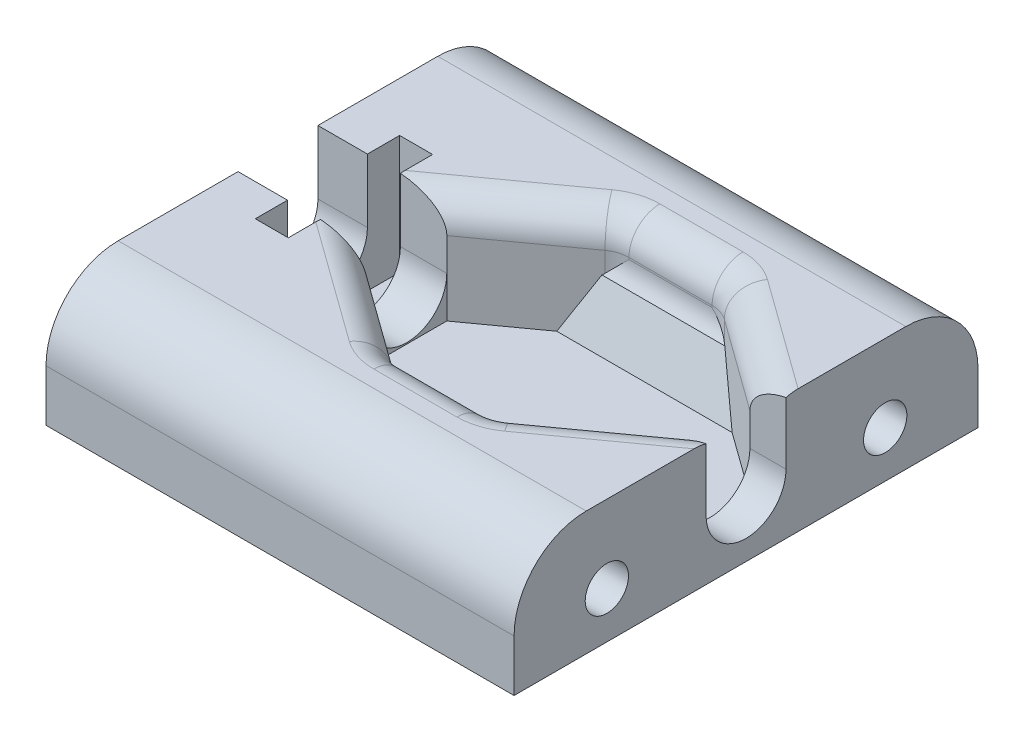
SolidWorks part; units mm, degrees
other "Markup1"
sketch "Sketch10" plane through (217, 42, -42) normal (0.057, 0.9883, -0.1416) x (-0.9984, 0.0574, -0.0017)
sketch "Sketch71" plane through (218, 42, -54.5) normal (0.057, 0.9883, -0.1416) x (-0.9984, 0.0574, -0.0017)
sketch "Sketch77" plane through (218, 42, -45) normal (0.057, 0.9883, -0.1416) x (-0.9984, 0.0574, -0.0017)
ref_plane "Front Plane" through (0, 0, 0) normal (0, 0, 1) x (1, 0, 0)
ref_plane "Top Plane" through (0, 0, 0) normal (0, 1, 0) x (1, 0, 0)
ref_plane "Right Plane" through (0, 0, 0) normal (1, 0, 0) x (0, 0, -1)
sketch "Sketch1" plane through (0, 0, 0) normal (0, 1, 0) x (1, 0, 0)
  line L1 (0, 0) -> (218, 0)
  line L2 (0, 0) -> (0, 45)
  line L3 (0, 45) -> (218, 45)
  line L4 (218, 0) -> (218, 45)
  dimension "D1" = 45
  dimension "D2" = 218
extrude "Boss-Extrude1" add sketch "Sketch1" along normal blind 42
sketch "Sketch7" plane through (0, 42, 0) normal (0, 1, 0) x (1, 0, 0)
  line L0 (218, 45) -> (0, 45) construction
  line L1 (9, 43.5) -> (127.2, 43.5)
  line L2 (9, 43.5) -> (9, 1.5)
  line L3 (9, 1.5) -> (127.2, 1.5)
  line L4 (127.2, 43.5) -> (127.2, 1.5)
  line L5 (0, 0) -> (218, 0) construction
  line L7 (0, 45) -> (0, 0) construction
  dimension "D1" = 1.5
  dimension "D2" = 1.5
  dimension "D3" = 9
  dimension "D4" = 118.2
extrude "Cut-Extrude17" cut sketch "Sketch7" against normal blind 21
sketch "Sketch4" plane through (218, 0, 0) normal (1, 0, 0) x (0, 0, -1)
  line L0 (0, 42) -> (45, 42) construction
  line L1 (18.625, 42) -> (26.375, 42)
  line L2 (18.625, 42) -> (18.625, 35.825)
  line L3 (18.625, 35.825) -> (26.375, 35.825)
  line L4 (26.375, 42) -> (26.375, 35.825)
  line L5 (0, 42) -> (0, 0) construction
  dimension "D4" = 6.175
  dimension "D1" = 0
  dimension "D2" = 18.625
  dimension "D3" = 7.75
extrude "Cut-Extrude14" cut sketch "Sketch4" against normal blind 97.8
sketch "Sketch5" plane through (218, 0, 0) normal (1, 0, 0) x (0, 0, -1)
  line L2 (0, 42) -> (0, 0) construction
  line L4 (18.625, 35.825) -> (26.375, 35.825) construction
  circle A0 centre (22.5, 35.825) radius 3.875
  dimension "D1" = 0
  dimension "D2" = 22.5
extrude "Cut-Extrude15" cut sketch "Sketch5" against normal blind 97.8
sketch "Sketch11" plane through (0, 42, 0) normal (0, 1, 0) x (1, 0, 0)
  line L1 (132, 29.5) -> (135.2, 29.5)
  line L2 (132, 29.5) -> (132, 15.5)
  line L3 (132, 15.5) -> (135.2, 15.5)
  line L4 (135.2, 29.5) -> (135.2, 15.5)
  line L6 (133.6, 29.5) -> (133.6, 15.5) construction
  line L7 (127.2, 26.375) -> (127.2, 18.625) construction
  line L9 (127.2, 22.5) -> (133.6, 22.5) construction
  point P19 (133.6, 22.5)
  dimension "D1" = 14
  dimension "D2" = 6.4
  dimension "D3" = 3.2
extrude "Cut-Extrude19" cut sketch "Sketch11" against normal blind 11.5
sketch "Sketch52" plane through (218, 0, 0) normal (1, 0, 0) x (0, 0, -1)
  line L0 (17.475, 42) -> (17.475, 35.825)
  line L1 (0, 42) -> (18.625, 42) construction
  line L2 (26.375, 42) -> (45, 42) construction
  line L3 (27.525, 42) -> (27.525, 35.825)
  line L5 (17.475, 42) -> (27.525, 42)
  line L7 (18.625, 42) -> (18.625, 35.825) construction
  line L8 (26.375, 35.825) -> (26.375, 42) construction
  line L9 (18.625, 38.9125) -> (17.475, 38.9125) construction
  line L10 (27.525, 38.9125) -> (26.375, 38.9125) construction
  arc A0 (17.475, 35.825) -> (27.525, 35.825) centre (22.5, 35.825) ccw
  dimension "D1" = 1.15
extrude "Cut-Extrude43" cut sketch "Sketch52" against normal blind 7
sketch "Sketch53" plane through (218, 0, 0) normal (1, 0, 0) x (0, 0, -1)
  line L0 (0, 42) -> (17.475, 42) construction
  line L1 (27.525, 42) -> (45, 42) construction
  circle A0 centre (9, 34.5) radius 2.1
  circle A1 centre (36, 34.5) radius 2.1
  arc A2 (17.475, 35.825) -> (27.525, 35.825) centre (22.5, 35.825) ccw construction
  arc A3 (17.475, 35.825) -> (27.525, 35.825) centre (22.5, 35.825) ccw construction
  dimension "D2" = 7.5
  dimension "D4" = 13.5
  dimension "D5" = 4.2
  dimension "D1" = 7.5
  dimension "D3" = 13.5
extrude "Cut-Extrude44" cut sketch "Sketch53" against normal blind 95
sketch "Sketch68" plane through (127.2, 0, 0) normal (-1, 0, 0) x (0, 0, 1)
  circle A0 centre (-9, 34.5) radius 2.65
  circle A1 centre (-36, 34.5) radius 2.65
  dimension "D1" = 5.3
extrude "Cut-Extrude57" cut sketch "Sketch68" against normal blind 28.3
ref_plane "Front" through (0, 21, 0) normal (0, 1, 0) x (1, 0, 0)
ref_plane "Top" through (127.2, 0, 0) normal (-1, 0, 0) x (0, 0, 1)
ref_plane "Right" through (0, 0, -22.5) normal (0, 0, 1) x (1, 0, 0)
sketch "Sketch14" plane through (0, 0, 0) normal (0, -1, 0) x (1, 0, 0)
  line L0 (0, -45) -> (0, 0) construction
  line L1 (9, -54.5) -> (89.5, -54.5)
  line L2 (9, -54.5) -> (9, -45)
  line L3 (9, 9.5) -> (89.5, 9.5)
  line L4 (89.5, -54.5) -> (89.5, -45)
  line L5 (218, -45) -> (0, -45) construction
  line L6 (89.5, -45) -> (218, -45)
  line L7 (218, -45) -> (218, 0)
  line L8 (218, 0) -> (89.5, 0)
  line L9 (0, 0) -> (218, 0) construction
  line L10 (9, 0) -> (0, 0)
  line L11 (0, 0) -> (0, -45)
  line L12 (0, -45) -> (9, -45)
  line L13 (9, 0) -> (9, 9.5)
  line L14 (89.5, 0) -> (89.5, 9.5)
  point P6 (0, -22.5)
  dimension "D1" = 64
  dimension "D2" = 80.5
  dimension "D3" = 9
  dimension "D4" = 9.5
extrude "Boss-Extrude2" add sketch "Sketch14" along normal blind 5
sketch "Sketch42" plane through (0, 0, 0) normal (0, 1, 0) x (1, 0, 0)
  line L0 (89.5, 0) -> (89.5, -9.5)
  line L1 (9, 45) -> (89.5, 45)
  line L2 (9, 45) -> (9, 54.5)
  line L3 (9, 54.5) -> (89.5, 54.5)
  line L4 (89.5, 45) -> (89.5, 54.5)
  line L5 (89.5, -9.5) -> (9, -9.5)
  line L6 (9, -9.5) -> (9, 0)
  line L7 (9, 0) -> (89.5, 0)
extrude "Boss-Extrude3" add sketch "Sketch42" along normal blind 35
extrude "Cut-Extrude32" cut sketch "Sketch38" against normal blind 4.7
sketch "Sketch38" plane through (127.2, -5, -22.5) normal (0, -1, 0) x (0, 0, -1)
  circle A3 centre (23.5, -61.2) radius 3.1
  circle A6 centre (10, -61.2) radius 3.1
extrude "Cut-Extrude34" cut sketch "Sketch40" against normal blind 9
sketch "Sketch40" plane through (127.2, -5, -22.5) normal (0, -1, 0) x (0, 0, -1)
  circle A3 centre (0, -33.7) radius 5.5
extrude "Cut-Extrude35" cut sketch "Sketch41" against normal blind 4
sketch "Sketch41" plane through (127.2, -5, -22.5) normal (0, -1, 0) x (0, 0, -1)
  circle A3 centre (20, -73.2) radius 5.75
  circle A6 centre (-20, -73.2) radius 5.75
fillet "Fillet1" radius 7 2 edges at (109, 42, -45) (109, 42, 0)
fillet "Fillet7" radius 5 2 edges at (49.25, 35, -54.5) (49.25, 35, 9.5)
extrude "Cut-Extrude39" cut sketch "Sketch47" against normal blind 7
sketch "Sketch47" plane through (127.2, -0.3, -22.5) normal (0, -1, 0) x (0, 0, -1)
  circle A0 centre (23.5, -61.2) radius 1.5
  circle A1 centre (10, -61.2) radius 1.5
sketch "Sketch49" plane through (0, 6.7, 0) normal (0, -1, 0) x (1, 0, 0)
  circle A0 centre (66, -32.5) radius 2.8
  circle A1 centre (66, -46) radius 2.8
  dimension "D1" = 5.6
extrude "Cut-Extrude41" cut sketch "Sketch49" against normal blind 33
sketch "Sketch55" [suppressed] plane through (223, 0, 0) normal (1, 0, 0) x (0, 0, -1)
  line L0 (42, -2) -> (42, 28.52)
  line L2 (42, 28.52) -> (3, 28.52)
  line L3 (3, 28.52) -> (3, -2)
  line L4 (3, -2) -> (42, -2)
  line L5 (45, 35) -> (45, -5) construction
  line L6 (45, -5) -> (0, -5) construction
  line L7 (0, 35) -> (0, -5) construction
  arc A1 (17.9, 35.82) -> (27.1, 35.82) centre (22.5, 35.82) ccw construction
  dimension "D1" = 3
  dimension "D2" = 3
  dimension "D3" = 3
  dimension "D4" = 7.3
extrude "Cut-Extrude46" [suppressed] cut sketch "Sketch55" against normal blind 55
sketch "Sketch56" plane through (0, -5, 0) normal (0, -1, 0) x (1, 0, 0)
  line L0 (127.2, -9) -> (127.2, -19.4)
  line L1 (127.2, -19.4) -> (143, -19.4)
  line L2 (143, -19.4) -> (143, -9)
  line L3 (143, -9) -> (127.2, -9)
  line L4 (0, 0) -> (0, -45) construction
  line L5 (218, 0) -> (89.5, 0) construction
  dimension "D1" = 127.2
  dimension "D2" = 10.4
  dimension "D3" = 15.8
  dimension "D4" = 9
extrude "Cut-Extrude47" cut sketch "Sketch56" against normal blind 32.15
sketch "Sketch57" plane through (0, -5, 0) normal (0, -1, 0) x (1, 0, 0)
  line L6 (127.2, -9) -> (127.2, -19.4) construction
  line L7 (127.2, -9) -> (122.2, -9)
  line L8 (127.2, -9) -> (127.2, -19.4)
  line L9 (127.2, -19.4) -> (122.2, -19.4)
  line L10 (122.2, -9) -> (122.2, -19.4)
  line L11 (143, -9) -> (127.2, -9) construction
  line L12 (127.2, -19.4) -> (143, -19.4) construction
  dimension "D4" = 5
extrude "Cut-Extrude48" cut sketch "Sketch57" against normal blind 15
extrude "Cut-Extrude49" cut sketch "Sketch58" against normal blind 10
sketch "Sketch58" plane through (127.2, 21, 0) normal (0, 0, 1) x (0, -1, 0)
  line L6 (-2.6328, 15.65) -> (-3.6672, 15.65)
  line L7 (-3.6672, 10.35) -> (-2.6328, 10.35)
  circle A4 centre (19.05, 2.8) radius 2.8
  circle A6 centre (10.15, 2.8) radius 2.05
  arc A12 (-2.6328, 10.35) -> (-2.6328, 15.65) centre (-3.15, 13) ccw
  arc A13 (-3.6672, 15.65) -> (-3.6672, 10.35) centre (-3.15, 13) ccw
sketch "Sketch59" plane through (0, 0, -19.4) normal (0, 0, 1) x (1, 0, 0)
  line L2 (137.55, 24.6672) -> (137.55, 23.6328) construction
  circle A0 centre (130, 1.95) radius 1.5
  circle A1 centre (130, 10.85) radius 0.95
  circle A2 centre (140.2, 24.15) radius 1.5
  circle A3 centre (130, 1.95) radius 2.8 construction
  circle A4 centre (130, 10.85) radius 2.05 construction
  arc A7 (142.85, 24.6672) -> (137.55, 24.6672) centre (140.2, 24.15) ccw construction
  dimension "D1" = 3
  dimension "D2" = 1.9
  dimension "D3" = 2.65
  dimension "D4" = 3
  dimension "D5" = 1.2
extrude "Cut-Extrude50" cut sketch "Sketch59" against normal blind 6.5
sketch "Sketch62" plane through (0, 0, 0) normal (-1, 0, 0) x (0, 0, 1)
  line L0 (0, -5) -> (-45, -5)
  line L1 (-45, -5) -> (-45, 35)
  line L3 (-38, 42) -> (-7, 42)
  line L4 (-38, 42) -> (-7, 42) construction
  line L5 (0, 35) -> (0, -5)
  arc A0 (0, 35) -> (-7, 42) centre (-7, 35) ccw
  arc A1 (-45, 35) -> (-38, 42) centre (-38, 35) cw
  point P13 (0, 42)
  dimension "D1" = 7
extrude "Cut-Extrude51" cut sketch "Sketch62" against normal blind 9
extrude "Cut-Extrude52" cut sketch "Sketch63" along normal blind 118.2
sketch "Sketch63" plane through (127.2, 21, -22.5) normal (-1, 0, 0) x (0, 0, -1)
  line L12 (-10.9597, -18.9503) -> (11.0403, -18.9503)
  line L17 (21.0403, -8.9503) -> (21.0403, 2.0497)
  line L18 (11.0403, 12.0497) -> (-10.9597, 12.0497)
  line L19 (-20.9597, 2.0497) -> (-20.9597, -8.9503)
  arc A16 (11.0403, -18.9503) -> (21.0403, -8.9503) centre (11.0403, -8.9503) ccw
  arc A17 (21.0403, 2.0497) -> (11.0403, 12.0497) centre (11.0403, 2.0497) ccw
  arc A18 (-10.9597, 12.0497) -> (-20.9597, 2.0497) centre (-10.9597, 2.0497) ccw
  arc A19 (-20.9597, -8.9503) -> (-10.9597, -18.9503) centre (-10.9597, -8.9503) ccw
extrude "Cut-Extrude53" cut sketch "Sketch64" against normal blind 14
sketch "Sketch64" plane through (127.2, -5, -22.5) normal (0, -1, 0) x (0, 0, -1)
  circle A3 centre (-1, -71.2) radius 1.5
extrude "Cut-Extrude54" cut sketch "Sketch65" against normal blind 9.95
sketch "Sketch65" plane through (127.2, 8.9503, -22.5) normal (0, 1, 0) x (0, 0, 1)
  circle A1 centre (1, -71.2) radius 2.8
extrude "Cut-Extrude55" cut sketch "Sketch66" against normal blind 25
sketch "Sketch66" plane through (127.2, -5, -22.5) normal (0, -1, 0) x (0, 0, -1)
  circle A3 centre (-20, -52.2) radius 1.5
extrude "Cut-Extrude56" cut sketch "Sketch67" against normal blind 7
sketch "Sketch67" plane through (9, 21, -22.5) normal (-1, 0, 0) x (0, 0, -1)
  circle A3 centre (27, -9) radius 1.45
  circle A6 centre (27, 21) radius 1.45
  circle A9 centre (-27, 21) radius 1.45
  circle A12 centre (-27, -9) radius 1.45
extrude "Cut-Extrude58" cut sketch "Sketch69" against normal blind 41 from offset 4 offset against normal yes
sketch "Sketch69" plane through (127.2, -5, -22.5) normal (0, -1, 0) x (0, 0, -1)
  circle A0 centre (-20, -52.2) radius 2.8
sketch "Sketch70" plane through (0, 42, 0) normal (0, 1, 0) x (1, 0, 0)
  line L0 (135.2, 26.375) -> (139.7, 26.375) construction
  line L1 (135.2, 26.375) -> (211, 26.375) construction
  line L3 (149.4, 33.375) -> (159.4, 33.375)
  line L4 (159.4, 33.375) -> (169.1, 26.375)
  line L5 (206.5, 26.375) -> (211, 26.375) construction
  line L9 (206.5, 18.625) -> (211, 18.625) construction
  line L10 (177.1, 26.375) -> (186.8, 33.375)
  line L11 (186.8, 33.375) -> (196.8, 33.375)
  line L12 (196.8, 33.375) -> (206.5, 26.375)
  line L13 (169.1, 26.375) -> (177.1, 26.375) construction
  line L14 (135.2, 18.625) -> (139.7, 18.625) construction
  line L15 (135.2, 18.625) -> (211, 18.625) construction
  line L16 (139.7, 18.625) -> (149.4, 11.625)
  line L17 (149.4, 11.625) -> (159.4, 11.625)
  line L18 (159.4, 11.625) -> (169.1, 18.625)
  line L19 (177.1, 18.625) -> (169.1, 18.625) construction
  line L23 (149.4, 33.375) -> (139.7, 26.375)
  line L24 (177.1, 18.625) -> (186.8, 11.625)
  line L25 (186.8, 11.625) -> (196.8, 11.625)
  line L26 (196.8, 11.625) -> (206.5, 18.625)
  line L27 (135.2, 26.375) -> (211, 26.375) construction
  line L28 (154.4, 33.375) -> (154.4, 26.375) construction
  line L29 (154.4, 11.625) -> (154.4, 18.625) construction
  line L30 (135.2, 18.625) -> (211, 18.625) construction
  line L33 (191.8, 11.625) -> (191.8, 18.625) construction
  line L34 (191.8, 33.375) -> (191.8, 26.375) construction
  line L35 (139.7, 26.375) -> (169.1, 26.375)
  line L37 (177.1, 26.375) -> (206.5, 26.375)
  line L38 (206.5, 18.625) -> (177.1, 18.625)
  line L39 (139.7, 18.625) -> (169.1, 18.625)
  point P1 (165.5537, 26.375)
  point P11 (168.8899, 26.375)
  point P18 (155.0833, 36.375)
  point P20 (147.8153, 36.375)
  point P23 (150.0803, 36.375)
  point P27 (149.3834, 36.375)
  point P28 (159.4021, 36.375)
  dimension "D1" = 10
  dimension "D2" = 7
  dimension "D3" = 8
  dimension "D4" = 4.5
extrude "Cut-Extrude59" cut sketch "Sketch70" against normal blind 6.175
fillet "Fillet17" radius 3 12 edges at (144.55, 42, -15.125) (164.25, 42, -15.125) (164.25, 42, -29.875) (144.55, 42, -29.875) (149.4, 38.9125, -11.625) (154.4, 35.825, -11.625) (159.4, 38.9125, -11.625) (154.4, 42, -11.625) (159.4, 38.9125, -33.375) (154.4, 35.825, -33.375) (149.4, 38.9125, -33.375) (154.4, 42, -33.375)
sketch "Sketch78" plane through (0, 35.825, 0) normal (0, 1, 0) x (1, 0, 0)
  line L0 (145.2429, 30.375) -> (163.5571, 30.375)
  line L1 (163.5571, 30.375) -> (169.1, 26.375)
  line L3 (139.7, 26.375) -> (145.2429, 30.375)
  line L12 (169.1, 26.375) -> (169.1, 18.625)
  line L13 (139.7, 26.375) -> (139.7, 18.625)
  line L15 (139.7, 18.625) -> (145.2429, 14.625)
  line L16 (145.2429, 14.625) -> (163.5571, 14.625)
  line L17 (163.5571, 14.625) -> (169.1, 18.625)
extrude "Cut-Extrude64" cut sketch "Sketch78" against normal blind 4
fillet "Fillet19" radius 3 12 edges at (181.95, 42, -15.125) (201.65, 42, -15.125) (201.65, 42, -29.875) (181.95, 42, -29.875) (186.8, 38.9125, -11.625) (191.8, 35.825, -11.625) (196.8, 38.9125, -11.625) (191.8, 42, -11.625) (196.8, 38.9125, -33.375) (191.8, 35.825, -33.375) (186.8, 38.9125, -33.375) (191.8, 42, -33.375)
sketch "Sketch79" plane through (0, 35.825, 0) normal (0, 1, 0) x (1, 0, 0)
  line L0 (182.6429, 30.375) -> (177.1, 26.375)
  line L1 (177.1, 26.375) -> (177.1, 18.625)
  line L2 (177.1, 18.625) -> (182.6429, 14.625)
  line L3 (182.6429, 14.625) -> (200.9571, 14.625)
  line L4 (200.9571, 14.625) -> (206.5, 18.625)
  line L5 (206.5, 18.625) -> (206.5, 26.375)
  line L6 (206.5, 26.375) -> (200.9571, 30.375)
  line L7 (200.9571, 30.375) -> (182.6429, 30.375)
extrude "Cut-Extrude65" cut sketch "Sketch79" against normal blind 4
chamfer "Chamfer1" distance 10 angle 45 2 edges at (191.8, 35.825, -30.375) (154.4, 35.825, -30.375)
chamfer "Chamfer2" distance 10 angle 45 2 edges at (191.8, 35.825, -14.625) (154.4, 35.825, -14.625)
sketch "Sketch76" plane through (0, 42, 0) normal (0, 1, 0) x (1, 0, 0)
  line L3 (169.1, 26.375) -> (177.1, 26.375) construction
  line L4 (127.2, 18.625) -> (132, 18.625) construction
  line L5 (173.1, 26.375) -> (173.1, 30.875) construction
  line L6 (129.6, 14.125) -> (129.6, 18.625) construction
  line L7 (158.4, 18.625) -> (164.6, 18.625) construction
  line L8 (129.6, 14.125) -> (129.6, 18.625) construction
  line L9 (127.2, 18.625) -> (132, 18.625) construction
  line L10 (129.6, 30.875) -> (129.6, 26.375) construction
  line L11 (127.2, 26.375) -> (132, 26.375) construction
  circle A0 centre (173.1, 30.875) radius 0.9
  circle A1 centre (129.6, 30.875) radius 0.9
  circle A2 centre (129.6, 14.125) radius 0.9
  circle A3 centre (129.6, 14.125) radius 0.9
  point P12 (129.6, 18.625)
  point P16 (173.1, 26.375)
  dimension "D1" = 1.8
  dimension "D2" = 4.5
sketch "Sketch72" plane through (9, 0, 0) normal (-1, 0, 0) x (0, 0, 1)
  line L0 (-54.5, -5) -> (-54.5, 30) construction
  line L1 (9.5, -5) -> (-54.5, -5)
  line L2 (9.5, -5) -> (9.5, 30)
  line L3 (9.5, 30) -> (-54.5, 30)
  line L4 (-54.5, -5) -> (-54.5, 30)
  arc A0 (-49.5, 35) -> (-54.5, 30) centre (-49.5, 30) ccw construction
extrude "Cut-Extrude61" cut sketch "Sketch72" along direction (-1, 0, 0) on the side against the normal through all and the other way blind 1 from surface starting at face at (9, 30, 5.95)
sketch "Sketch74" plane through (0, 30, 0) normal (0, -1, 0) x (1, 0, 0)
  line L1 (9, 9.5) -> (127.2, 9.5)
  line L2 (9, 9.5) -> (9, -54.5)
  line L3 (9, -54.5) -> (127.2, -54.5)
  line L4 (127.2, 9.5) -> (127.2, -54.5)
  line L5 (127.2, -1.5) -> (127.2, -43.5402) construction
extrude "Cut-Extrude62" cut sketch "Sketch74" against normal through all
sketch "Sketch81" plane through (0, 42, 0) normal (0, 1, 0) x (1, 0, 0)
  line L0 (172.6, 45) -> (172.6, 0)
  line L1 (127.2, 45) -> (218, 45) construction
  line L2 (218, 0) -> (127.2, 0) construction
  line L3 (172.6, 0) -> (218, 0)
  line L4 (218, 0) -> (218, 45)
  line L5 (218, 45) -> (172.6, 45)
extrude "Cut-Extrude66" cut sketch "Sketch81" against normal blind 12
